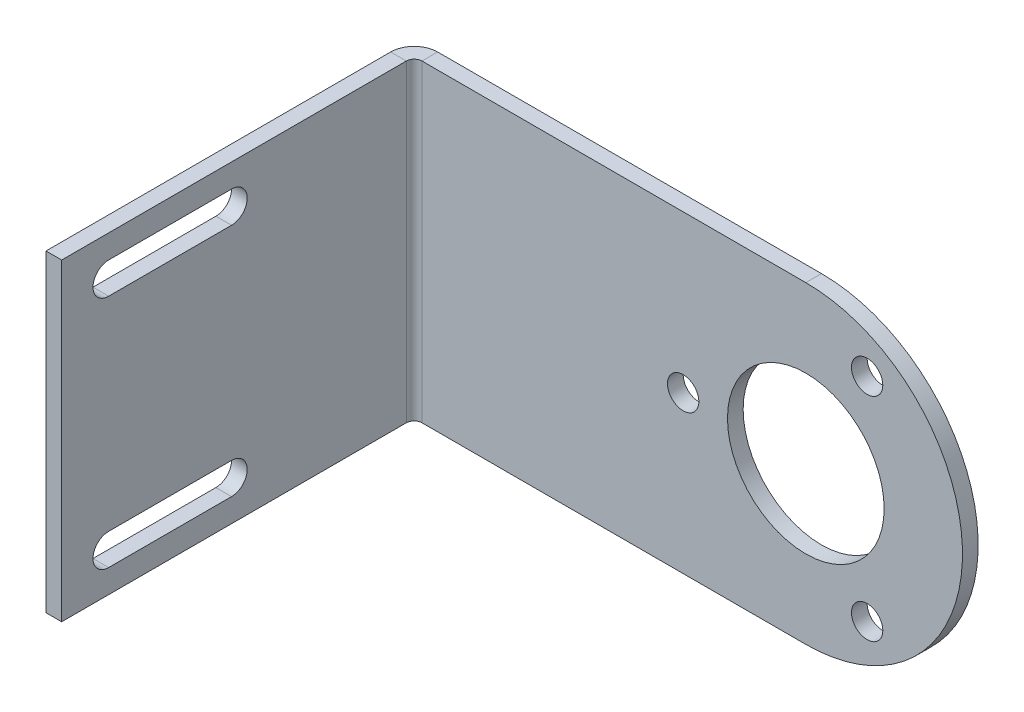
SolidWorks part; units mm, degrees
note: The reader was unsure of these and kept them because the rebuilt part matched: flange length of "边线-法兰1".
ref_plane "前视基准面" through (0, 0, 0) normal (0, 0, 1) x (1, 0, 0)
ref_plane "上视基准面" through (0, 0, 0) normal (0, 1, 0) x (1, 0, 0)
ref_plane "右视基准面" through (0, 0, 0) normal (1, 0, 0) x (0, 0, -1)
sketch "草图1" plane through (0, 0, 0) normal (0, 0, 1) x (1, 0, 0)
  line L0 (-76.0654, -10.8807) -> (107.3471, -10.8807) construction
  line L1 (-31.4154, 9.1193) -> (18.5846, 9.1193)
  line L2 (-31.4154, 9.1193) -> (-31.4154, -30.8807)
  line L3 (-31.4154, -30.8807) -> (18.5846, -30.8807)
  line L4 (18.5846, -43.4468) -> (18.5846, 32.2175) construction
  arc A1 (18.5846, -30.8807) -> (18.5846, 9.1193) centre (18.5846, -10.8807) ccw
base flange "基体-法兰1" sketch "草图1" thickness 2 reverse thickness direction no parameters "D1"=1
sketch "草图7" plane through (0, 0, 0) normal (0, 0, 1) x (1, 0, 0)
  line L0 (18.5846, 13.5688) -> (18.5846, -39.417) construction
  line L1 (-7.6912, -10.8807) -> (44.1104, -10.8807) construction
  line L2 (26.4129, 2.6783) -> (26.4129, -24.4397) construction
  line L3 (26.4129, -24.4397) -> (2.928, -10.8807) construction
  line L4 (2.928, -10.8807) -> (26.4129, 2.6783) construction
  circle A0 centre (18.5846, -10.8807) radius 20 construction
  arc A1 (18.5846, -30.8807) -> (18.5846, 9.1193) centre (18.5846, -10.8807) ccw construction
  circle A2 centre (18.5846, -10.8807) radius 10
  circle A3 centre (18.5846, -10.8807) radius 15.6566 construction
  circle A4 centre (2.928, -10.8807) radius 2
  circle A5 centre (26.4129, 2.6783) radius 2
  circle A6 centre (26.4129, -24.4397) radius 2
  dimension "D1" = 40
  dimension "D2" = 20
  dimension "D3" = 4
  dimension "D4" = 4
  dimension "D5" = 4
extrude "切除-拉伸1" cut sketch "草图7" against normal through all normal cut yes
edge flange "边线-法兰1" sketch "草图10" flange angle 90 flange length 45 flange position material outside bend radius 1 thickness 2 parameters "D6"=10
sketch "草图10" plane through (-31.4154, 0, 0) normal (-1, 0, 0) x (0, -1, 0)
  line L0 (-9.1193, 0) -> (30.8807, 0) construction
  line L1 (-9.1193, 0) -> (30.8807, 0)
  line L2 (-9.1193, 0) -> (-9.1193, 45)
  line L3 (-9.1193, 45) -> (30.8807, 45)
  line L4 (30.8807, 45) -> (30.8807, 0)
bend "边线折弯1" bend radius 1 bend angle 90 parameters "D5"=1
sketch "草图11" plane through (-31.4154, 0, 0) normal (1, 0, 0) x (0, 0, -1)
  line L0 (-39, 4.1193) -> (-23.3139, 4.1193) construction
  line L1 (-39, 6.1193) -> (-23.3139, 6.1193)
  line L2 (-39, 2.1193) -> (-23.3139, 2.1193)
  line L3 (-39, -25.8807) -> (-23.3139, -25.8807) construction
  line L4 (-39, -27.8807) -> (-23.3139, -27.8807)
  line L5 (-39, -23.8807) -> (-23.3139, -23.8807)
  line L6 (-45, -10.8807) -> (-1, -10.8807) construction
  line L7 (-45, -30.8807) -> (-45, 9.1193) construction
  line L8 (-1, 9.1193) -> (-1, -30.8807) construction
  line L9 (-45, 9.1193) -> (-1, 9.1193) construction
  line L10 (-1, -30.8807) -> (-45, -30.8807) construction
  arc A0 (-39, 6.1193) -> (-39, 2.1193) centre (-39, 4.1193) ccw
  arc A1 (-23.3139, 2.1193) -> (-23.3139, 6.1193) centre (-23.3139, 4.1193) ccw
  arc A2 (-39, -27.8807) -> (-39, -23.8807) centre (-39, -25.8807) cw
  arc A3 (-23.3139, -23.8807) -> (-23.3139, -27.8807) centre (-23.3139, -25.8807) cw
  point P2 (-31.157, 4.1193)
  point P9 (-31.157, -25.8807)
  dimension "D2" = 6
  dimension "D3" = 2
  dimension "D1" = 3
extrude "切除-拉伸2" cut sketch "草图11" against normal through all normal cut yes
sketch "折弯-线1" plane through (0, 0, 0) normal (0, 1, 0) x (1, 0, 0)
sketch "边界框1" plane through (0, 0, 0) normal (0, 1, 0) x (1, 0, 0)
sheet metal parameters "钣金6" thickness 2 parameters "D1"=1
flat pattern "平板型式6" [suppressed]
sketch "折弯-线2" plane through (0, 0, 0) normal (0, 1, 0) x (1, 0, 0)
sketch "边界框2" [suppressed] plane through (0, 0, 0) normal (0, 1, 0) x (1, 0, 0)
sheet metal parameters "钣金7" thickness 2 parameters "D1"=1
flat pattern "平板型式6"
sketch "折弯-线2" plane through (0, 0, 0) normal (0, 1, 0) x (1, 0, 0)
sketch "边界框2" [suppressed] plane through (0, 0, 0) normal (0, 1, 0) x (1, 0, 0)
sheet metal parameters "钣金8" thickness 2 parameters "D1"=1
flat pattern "平板型式6" [suppressed]
sketch "折弯-线2" plane through (0, 0, 0) normal (0, 1, 0) x (1, 0, 0)
sketch "边界框2" [suppressed] plane through (0, 0, 0) normal (0, 1, 0) x (1, 0, 0)
bend of the flat pattern "展开-<边线折弯1>1"
sheet metal parameters "钣金9" thickness 2 parameters "D1"=1
flat pattern "平板型式6" [suppressed]
sketch "折弯-线2" plane through (0, 0, 0) normal (0, 1, 0) x (1, 0, 0)
sketch "边界框2" [suppressed] plane through (0, 0, 0) normal (0, 1, 0) x (1, 0, 0)
bend of the flat pattern "展开-<边线折弯1>1"
